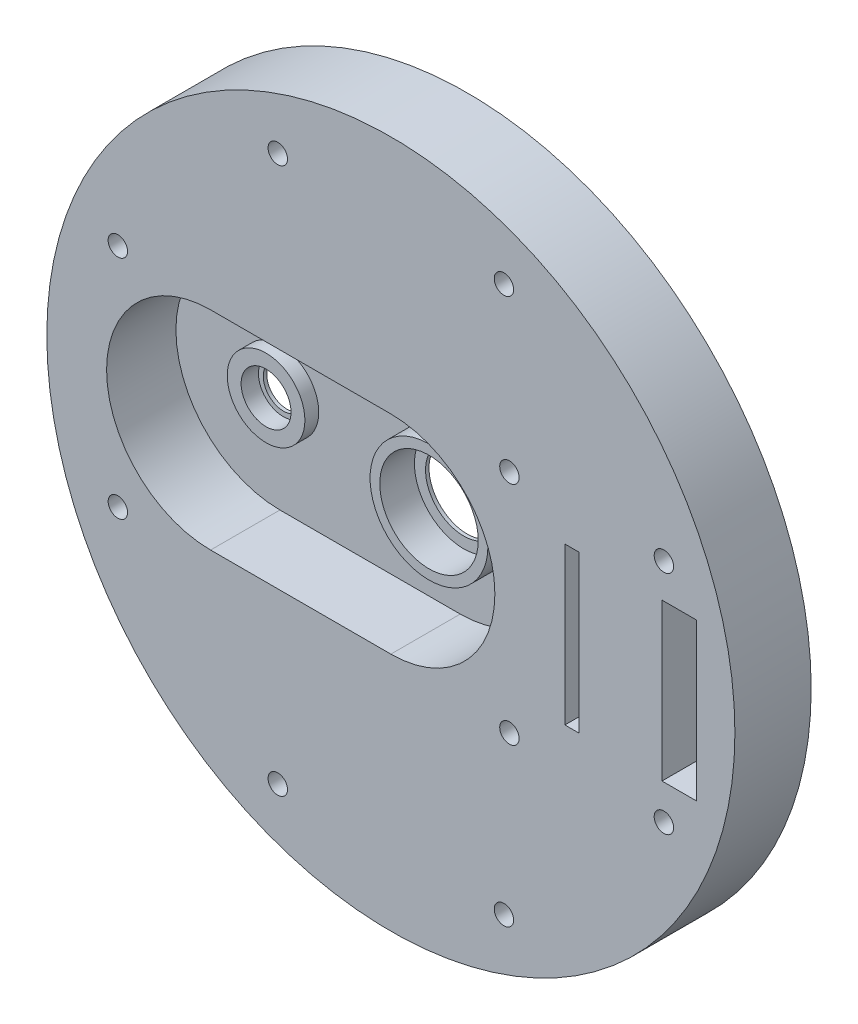
SolidWorks part; units mm, degrees
material "Nylon 101 90%"
ref_plane "Front Plane" through (0, 0, 0) normal (0, 0, 1) x (1, 0, 0)
ref_plane "Top Plane" through (0, 0, 0) normal (0, 1, 0) x (1, 0, 0)
ref_plane "Right Plane" through (0, 0, 0) normal (1, 0, 0) x (0, 0, -1)
sketch "Sketch1" plane through (0, 0, 0) normal (0, 0, 1) x (1, 0, 0)
  circle A0 centre (0, 0) radius 49.62
  dimension "D3" = 99.24
extrude "Base" add sketch "Sketch1" along normal blind 1
sketch "Sketch6" plane through (0, 0, 1) normal (0, 0, 1) x (1, 0, 0)
  line L2 (0, 0) -> (14, 0) construction
  line L3 (-26, 15) -> (0, 15)
  line L4 (0, -13.1) -> (0, 13.1) construction
  line L5 (-9.1, -13.1) -> (28.9, 13.1) construction
  line L8 (28.9, 13.1) -> (-9.1, 13.1) construction
  line L9 (28.9, -13.1) -> (28.9, 13.1) construction
  line L10 (-9.1, -13.1) -> (28.9, -13.1) construction
  line L11 (-9.1, 13.1) -> (-9.1, -13.1) construction
  line L12 (-26, -15) -> (0, -15)
  line L13 (0, 14) -> (0, 15) construction
  line L14 (0, -14) -> (0, -15) construction
  line L15 (-26, 14) -> (-26, 15) construction
  line L16 (-26, -14) -> (-26, -15) construction
  arc A0 (-26, 14) -> (-26, -14) centre (-26, 0) ccw construction
  arc A1 (-26, 15) -> (-26, -15) centre (-26, 0) ccw
  arc A3 (0, -15) -> (0, 15) centre (0, 0) ccw
  circle A5 centre (0, 0) radius 49.62 construction
  arc A6 (0, -14) -> (0, 14) centre (0, 0) ccw construction
  circle A7 centre (0, 0) radius 49.62
  arc A8 (0, -14) -> (0, 14) centre (0, 0) ccw construction
  circle A9 centre (0, 0) radius 49.62
  circle A11 centre (-26, 0) radius 13 construction
  circle A12 centre (0, 0) radius 13 construction
  point P2 (9.9, 0)
  point P26 (0, 0)
  dimension "D3" = 28
  dimension "D7" = 26
  dimension "D4" = 38
  dimension "D1" = 9.1
  dimension "D5" = 26.2
  dimension "D8" = 1
  dimension "D6" = 0
extrude "Walls" add sketch "Sketch6" along normal blind 10
ref_axis "Lower tube" through (9.9, 0, 1) along (0, 0, 1)
sketch "Sketch8" plane through (0, 0, 1) normal (0, 0, 1) x (1, 0, 0)
  circle A0 centre (-26, 0) radius 3.6
  dimension "D1" = 7.2
extrude "Pinion bearing pocket" cut sketch "Sketch8" against normal blind 0.5
sketch "Sketch9" plane through (0, 0, 0.5) normal (0, 0, 1) x (1, 0, 0)
  circle A0 centre (-26, 0) radius 2.9
  dimension "D1" = 5.8
extrude "Pinion bearing hole" cut sketch "Sketch9" against normal up to next
sketch "Sketch10" plane through (0, 0, 1) normal (0, 0, 1) x (1, 0, 0)
  circle A0 centre (-26, 0) radius 3.6 construction
  circle A1 centre (-26, 0) radius 3.6
  circle A2 centre (-26, 0) radius 5.6
  dimension "D1" = 2
extrude "Taller pinion bearing pocket" add sketch "Sketch10" along normal blind 2
sketch "Sketch11" plane through (0, 0, 1) normal (0, 0, 1) x (1, 0, 0)
  circle A0 centre (0, 0) radius 7.1
  dimension "D1" = 14.2
extrude "Gear bearing pocket" cut sketch "Sketch11" against normal up to surface (0.5 mm away) up to face at (-23.1, 0, 0.5)
sketch "Sketch12" plane through (0, 0, 0.5) normal (0, 0, 1) x (1, 0, 0)
  circle A0 centre (0, 0) radius 5.5
  circle A1 centre (0, 0) radius 7.1 construction
  dimension "D1" = 1.6
extrude "Gear bearing hole" cut sketch "Sketch12" against normal up to next
sketch "Sketch13" plane through (0, 0, 1) normal (0, 0, 1) x (1, 0, 0)
  circle A0 centre (0, 0) radius 8.5
  circle A1 centre (0, 0) radius 7.1 construction
  circle A2 centre (0, 0) radius 7.1
  dimension "D1" = 17
extrude "Taller gear bearing pocket" add sketch "Sketch13" along normal blind 4.5
sketch "Sketch16" plane through (0, 0, 11) normal (0, 0, 1) x (1, 0, 0)
  line L0 (0, 0) -> (-26, 0) construction
  line L1 (0, 0) -> (-39.3757, 16.31) construction
  line L2 (0, 0) -> (-16.31, 39.3757) construction
  circle A0 centre (0, 0) radius 42.62 construction
  circle A1 centre (0, 0) radius 49.62 construction
  circle A2 centre (-39.3757, 16.31) radius 1.4
  circle A3 centre (-16.31, 39.3757) radius 1.4
  circle A4 centre (16.31, 39.3757) radius 1.4
  circle A5 centre (39.3757, 16.31) radius 1.4
  circle A6 centre (39.3757, -16.31) radius 1.4
  circle A7 centre (16.31, -39.3757) radius 1.4
  circle A8 centre (-16.31, -39.3757) radius 1.4
  circle A9 centre (-39.3757, -16.31) radius 1.4
  point P26 (0, 0)
  dimension "D1" = 7
  dimension "D2" = 22.5
  dimension "D4" = 2.8
  dimension "D3" = 45
  dimension "D5" = 8
extrude "Screw holes" cut sketch "Sketch16" against normal up to next
sketch "Sketch17" plane through (0, 0, 11) normal (0, 0, 1) x (1, 0, 0)
  line L0 (48.797, 9) -> (12, 9)
  line L1 (48.797, -9) -> (12, -9)
  line L2 (15, 0) -> (49.62, 0) construction
  circle A0 centre (0, 0) radius 49.62 construction
  arc A1 (0, -15) -> (0, 15) centre (0, 0) ccw construction
  arc A2 (0, -15) -> (0, 15) centre (0, 0) ccw construction
  arc A3 (12, -9) -> (12, 9) centre (0, 0) ccw
  arc A4 (48.797, -9) -> (48.797, 9) centre (0, 0) ccw
  point P12 (49.62, 0)
  point P13 (15, 0)
  dimension "D1" = 18
extrude "Flex exit" [suppressed] cut sketch "Sketch17" against normal blind 2
sketch "Sketch18" plane through (0, 0, 0) normal (0, 0, 1) x (1, 0, 0)
  line L0 (25.1, 11.3) -> (27.1, 11.3) construction
  line L1 (25.1, -11.3) -> (25.1, 11.3) construction
  line L2 (27.1, -11.3) -> (25.1, -11.3) construction
  line L3 (27.1, 11.3) -> (27.1, -11.3) construction
  line L4 (25.1, 11.3) -> (27.1, 11.3)
  line L5 (25.1, -11.3) -> (25.1, 11.3)
  line L6 (27.1, -11.3) -> (25.1, -11.3)
  line L7 (27.1, 11.3) -> (27.1, -11.3)
extrude "Flex cable" cut sketch "Sketch18" along normal through all
sketch "Sketch19" plane through (0, 0, 0) normal (0, 0, 1) x (1, 0, 0)
  line L0 (25.1, 11.3) -> (25.1, 16.3) construction
  line L1 (25.1, 16.3) -> (17.1, 16.3) construction
  line L2 (25.1, -16.3) -> (25.1, -11.3) construction
  line L3 (27.1, -11.3) -> (39.1, -11.3) construction
  line L4 (39.1, -11.3) -> (39.1, 11.3)
  line L5 (39.1, 11.3) -> (27.1, 11.3) construction
  line L6 (25.1, -16.3) -> (17.1, -16.3) construction
  line L7 (17.1, 16.3) -> (17.1, -16.3) construction
  line L8 (44.1, -11.3) -> (44.1, 11.3)
  line L9 (44.1, 11.3) -> (39.1, 11.3)
  line L10 (44.1, -11.3) -> (39.1, -11.3)
  circle A1 centre (17.1, 16.3) radius 1.4
  circle A2 centre (17.1, -16.3) radius 1.4
  circle A4 centre (39.3757, -16.31) radius 1.4 construction
  point P0 (25.1, 13.8)
  dimension "D3" = 5
  dimension "D4" = 12
  dimension "D1" = 5
  dimension "D2" = 8
extrude "Cut-Extrude1" cut sketch "Sketch19" along normal up to next
